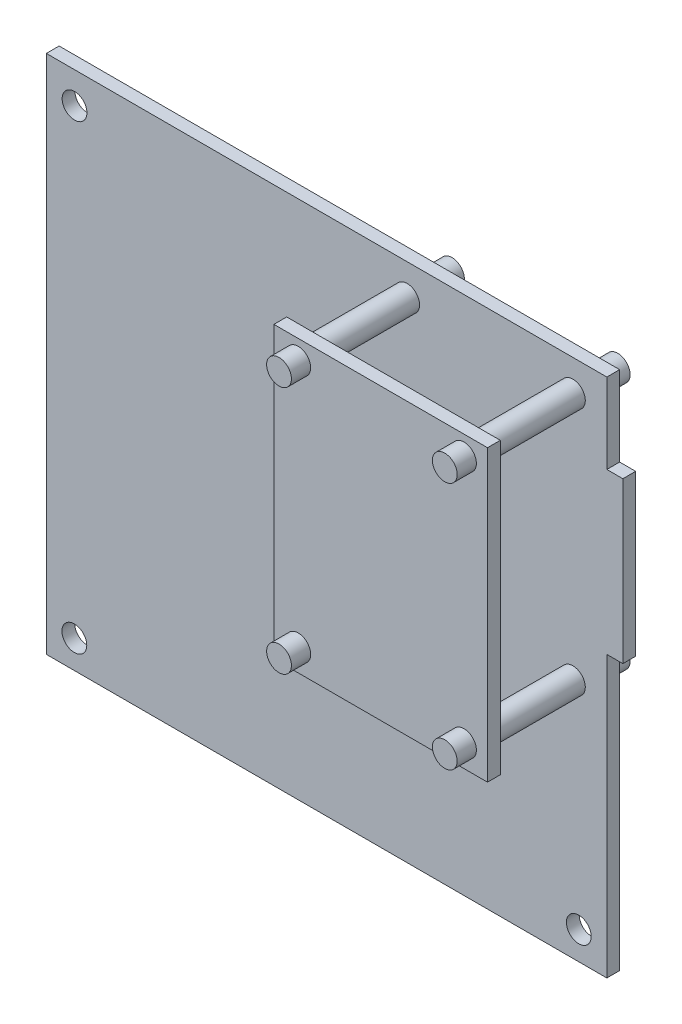
SolidWorks part; units mm, degrees
ref_plane "Front Plane" through (0, 0, 0) normal (0, 0, 1) x (1, 0, 0)
ref_plane "Top Plane" through (0, 0, 0) normal (0, 1, 0) x (1, 0, 0)
ref_plane "Right Plane" through (0, 0, 0) normal (1, 0, 0) x (0, 0, -1)
other "Center of Mass"
sketch "Sketch1" plane through (0, 0, 0) normal (0, 0, 1) x (1, 0, 0)
  line L0 (70, 55) -> (70, 65)
  line L1 (0, 0) -> (70, 0)
  line L2 (0, 0) -> (0, 65)
  line L3 (0, 65) -> (70, 65)
  line L4 (70, 0) -> (70, 35)
  line L5 (70, 55) -> (72, 55)
  line L7 (70, 35) -> (72, 35)
  line L8 (72, 55) -> (72, 35)
  circle A0 centre (3.523, 61.1) radius 1.55
  circle A1 centre (3.5, 3.5) radius 1.55
  circle A2 centre (66.5, 3.5) radius 1.55
  circle A3 centre (45.06, 61.1) radius 1.55
  circle A4 centre (65.76, 61.1) radius 1.55
  circle A5 centre (45.06, 30.1) radius 1.55
  circle A6 centre (65.76, 30.1) radius 1.55
  dimension "D3" = 3.1
  dimension "D4" = 3.1
  dimension "D5" = 3.1
  dimension "D12" = 3.1
  dimension "D14" = 3.1
  dimension "D15" = 3.1
  dimension "D16" = 3.1
  dimension "D1" = 70
  dimension "D2" = 65
  dimension "D6" = 3.5
  dimension "D7" = 3.5
  dimension "D8" = 3.5
  dimension "D9" = 3.5
  dimension "D10" = 3.523
  dimension "D11" = 3.9
  dimension "D13" = 3.9
  dimension "D17" = 20.7
  dimension "D18" = 20.7
  dimension "D19" = 31
  dimension "D20" = 4.24
  dimension "D21" = 4.24
  dimension "D22" = 20
  dimension "D23" = 10
  dimension "D24" = 2
extrude "Boss-Extrude1" add sketch "Sketch1" along normal blind 1.6
extrude "Boss-Extrude2" add sketch "Sketch1<3>" against normal blind 4 separate body contours A6 | A3 | A4 | A5 region at (65.76, 30.1, 0)
sketch "Sketch1<3>" plane through (0, 0, 0) normal (0, 0, 1) x (1, 0, 0) same geometry as "Sketch1"
extrude "Boss-Extrude3" add sketch "Sketch1<4>" along normal blind 17.6 contours A3 | A4 | A5 | A6 region at (45.06, 61.1, 0) region at (65.76, 61.1, 0) region at (45.06, 30.1, 0) region at (65.76, 30.1, 0)
sketch "Sketch1<4>" plane through (0, 0, 0) normal (0, 0, 1) x (1, 0, 0) same geometry as "Sketch1"
sketch "Sketch2" plane through (0, 0, 1.6) normal (0, 0, 1) x (1, 0, 0)
  line L1 (68.6953, 27.3277) -> (42.0173, 27.3277)
  line L2 (68.6953, 27.3277) -> (68.6953, 63.5033)
  line L3 (68.6953, 63.5033) -> (42.0173, 63.5033)
  line L4 (42.0173, 27.3277) -> (42.0173, 63.5033)
extrude "Boss-Extrude4" add sketch "Sketch2" along normal blind 1.6 from offset 12
